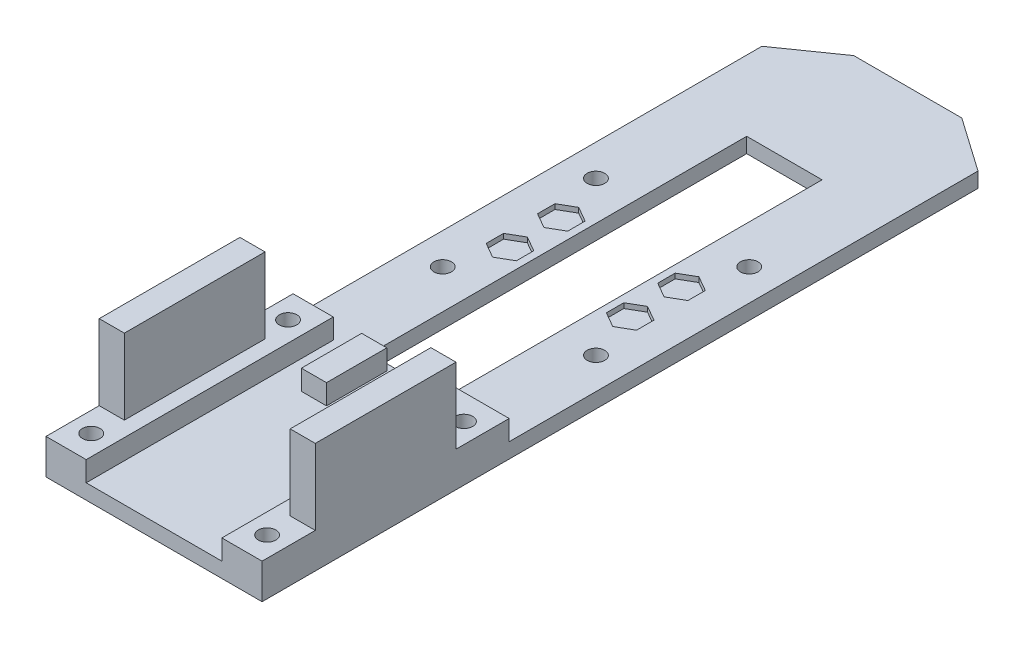
SolidWorks part; units mm, degrees
material "ABS"
ref_plane "Front Plane" through (0, 0, 0) normal (0, 0, 1) x (1, 0, 0)
ref_plane "Top Plane" through (0, 0, 0) normal (0, 1, 0) x (1, 0, 0)
ref_plane "Right Plane" through (0, 0, 0) normal (1, 0, 0) x (0, 0, -1)
sketch "Sketch1" plane through (0, 0, 0) normal (0, 1, 0) x (1, 0, 0)
  line L1 (21.5, -75) -> (-21.5, -75)
  line L2 (21.5, -75) -> (21.5, 75)
  line L3 (21.5, 75) -> (-21.5, 75)
  line L4 (-21.5, -75) -> (-21.5, 75)
  line L5 (21.5, -75) -> (-21.5, 75) construction
  line L6 (21.5, 75) -> (-21.5, -75) construction
  point P0 (0, 0)
  dimension "D1" = 150
  dimension "D2" = 43
extrude "Boss-Extrude1" add sketch "Sketch1" along normal blind 3
sketch "Sketch2" plane through (0, 3, 0) normal (0, 1, 0) x (1, 0, 0)
  line L0 (0, 75) -> (0, 38.94) construction
  line L1 (21.5, 75) -> (-21.5, 75) construction
  line L2 (0, 75) -> (15.25, 75) construction
  line L3 (15.25, 75) -> (15.25, 28.19) construction
  line L5 (15.25, 28.19) -> (-15.25, 28.19) construction
  line L6 (15.25, 28.19) -> (15.25, -2.31) construction
  line L7 (15.25, -2.31) -> (-15.25, -2.31) construction
  line L8 (-15.25, 28.19) -> (-15.25, -2.31) construction
  circle A0 centre (15.25, 28.19) radius 1.75
  circle A1 centre (-15.25, 28.19) radius 1.75
  circle A2 centre (-15.25, -2.31) radius 1.75
  circle A3 centre (15.25, -2.31) radius 1.75
  dimension "D6" = 3.5
  dimension "D7" = 3.5
  dimension "D8" = 3.5
  dimension "D9" = 3.5
  dimension "D1" = 36.06
  dimension "D2" = 15.25
  dimension "D3" = 46.81
  dimension "D4" = 30.5
  dimension "D5" = 30.5
extrude "Cut-Extrude1" cut sketch "Sketch2" against normal blind 10
sketch "Sketch3" plane through (0, 3, 0) normal (0, 1, 0) x (1, 0, 0)
  line L0 (-15.25, 28.19) -> (15.25, -2.31) construction
  line L1 (-15.25, 28.19) -> (15.25, 28.19) construction
  line L2 (-15.25, 28.19) -> (-15.25, -2.31) construction
  line L3 (-15.25, -2.31) -> (15.25, -2.31) construction
  line L4 (15.25, 28.19) -> (15.25, -2.31) construction
  line L6 (7.5, 50.44) -> (-7.5, 50.44)
  line L7 (7.5, 50.44) -> (7.5, -24.56)
  line L8 (7.5, -24.56) -> (-7.5, -24.56)
  line L9 (-7.5, 50.44) -> (-7.5, -24.56)
  line L10 (7.5, 50.44) -> (-7.5, -24.56) construction
  line L11 (7.5, -24.56) -> (-7.5, 50.44) construction
  point P6 (0, 12.94)
  dimension "D1" = 75
  dimension "D2" = 15
extrude "Cut-Extrude2" cut sketch "Sketch3" against normal blind 10
sketch "Sketch4" plane through (0, 3, 0) normal (0, 1, 0) x (1, 0, 0)
  line L0 (0, -24.56) -> (2.65, -24.56) construction
  line L1 (-7.5, -24.56) -> (7.5, -24.56) construction
  line L2 (2.65, -24.56) -> (2.65, -25.83) construction
  line L3 (8.15, -25.83) -> (-2.85, -25.83) construction
  line L4 (8.15, -37.83) -> (-2.85, -37.83) construction
  line L5 (-2.85, -25.83) -> (-7.85, -25.83)
  line L6 (-2.85, -25.83) -> (-2.85, -37.83)
  line L7 (-2.85, -37.83) -> (-7.85, -37.83)
  line L8 (-7.85, -25.83) -> (-7.85, -37.83)
  line L9 (8.15, -25.83) -> (13.15, -25.83)
  line L10 (8.15, -25.83) -> (8.15, -37.83)
  line L11 (8.15, -37.83) -> (13.15, -37.83)
  line L12 (13.15, -25.83) -> (13.15, -37.83)
  line L14 (2.65, -37.83) -> (6.7668, -37.83)
  line L15 (2.65, -37.83) -> (2.65, -36.33)
  line L16 (2.65, -36.33) -> (6.7668, -36.33)
  line L17 (6.7668, -37.83) -> (6.7668, -36.33)
  line L18 (2.65, -37.83) -> (6.7668, -37.83)
  line L19 (2.65, -37.83) -> (2.65, -41.33)
  line L20 (2.65, -41.33) -> (6.7668, -41.33)
  line L21 (6.7668, -37.83) -> (6.7668, -41.33)
  point P8 (2.65, -25.83)
  dimension "D1" = 2.65
  dimension "D2" = 1.27
  dimension "D3" = 11
  dimension "D4" = 5
  dimension "D5" = 5
  dimension "D6" = 12
  dimension "D7" = 12
  dimension "D8" = 1.5
  dimension "D9" = 3.5
extrude "Boss-Extrude2" add sketch "Sketch4" along normal blind 4 contours L6 L5 L8 L7 | L10 L9 L12 L11 | L19 L18 L21 L20 | L15 L14 L17 L16
sketch "Sketch5" plane through (0, 3, 0) normal (0, 1, 0) x (1, 0, 0)
  line L0 (-7.85, -25.83) -> (-21.5, -25.83) construction
  line L1 (-21.5, 75) -> (-21.5, -75) construction
  line L2 (13.15, -25.83) -> (21.5, -25.83) construction
  line L3 (21.5, -75) -> (21.5, 75) construction
  line L4 (-21.5, -75) -> (21.5, -75) construction
  line L5 (-21.5, -25.83) -> (-13.5, -25.83)
  line L6 (-21.5, -25.83) -> (-21.5, -75)
  line L7 (-21.5, -75) -> (-13.5, -75)
  line L8 (-13.5, -25.83) -> (-13.5, -75)
  line L10 (21.5, -25.83) -> (13.5, -25.83)
  line L11 (21.5, -25.83) -> (21.5, -75)
  line L12 (21.5, -75) -> (13.5, -75)
  line L13 (13.5, -25.83) -> (13.5, -75)
  dimension "D1" = 8
  dimension "D2" = 8
extrude "Boss-Extrude3" add sketch "Sketch5" along normal blind 4
sketch "Sketch7" plane through (0, 3, 0) normal (0, 1, 0) x (1, 0, 0)
  line L1 (13.15, -37.83) -> (13.5, -37.83)
  line L2 (13.15, -37.83) -> (13.15, -25.83)
  line L3 (13.15, -25.83) -> (13.5, -25.83)
  line L4 (13.5, -37.83) -> (13.5, -25.83)
extrude "Boss-Extrude4" add sketch "Sketch7" along normal blind 4
sketch "Sketch8" plane through (0, 7, 0) normal (0, 1, 0) x (1, 0, 0)
  line L0 (21.5, -75) -> (17.5, -75) construction
  line L1 (13.5, -75) -> (21.5, -75) construction
  line L2 (17.5, -75) -> (17.5, -70) construction
  line L3 (21.5, -25.83) -> (-21.5, -25.83) construction
  line L4 (0, -25.83) -> (0, -75) construction
  line L5 (-13.5, -75) -> (13.5, -75) construction
  line L6 (21.5, -50.415) -> (-21.5, -50.415) construction
  line L7 (21.5, -75) -> (21.5, -25.83) construction
  line L8 (-21.5, -25.83) -> (-21.5, -75) construction
  circle A0 centre (17.5, -70) radius 1.75
  circle A1 centre (17.5, -30.83) radius 1.75
  circle A2 centre (-17.5, -70) radius 1.75
  circle A3 centre (-17.5, -30.83) radius 1.75
  dimension "D2" = 3.5
  dimension "D1" = 5
extrude "Cut-Extrude3" cut sketch "Sketch8" against normal through all
sketch "Sketch9" plane through (0, 7, 0) normal (0, 1, 0) x (1, 0, 0)
  line L0 (21.5, -75) -> (21.5, -64.41) construction
  line L1 (21.5, -75) -> (21.5, -25.83) construction
  line L2 (0, -75) -> (0, -24.56) construction
  line L3 (21.5, -64.41) -> (16.5, -64.41)
  line L4 (21.5, -64.41) -> (21.5, -36.41)
  line L5 (21.5, -36.41) -> (16.5, -36.41)
  line L6 (16.5, -64.41) -> (16.5, -36.41)
  line L7 (-13.5, -75) -> (13.5, -75) construction
  line L8 (-7.5, -24.56) -> (7.5, -24.56) construction
  line L9 (-21.5, -36.41) -> (-16.5, -36.41)
  line L10 (-16.5, -64.41) -> (-16.5, -36.41)
  line L11 (-21.5, -64.41) -> (-16.5, -64.41)
  line L12 (-21.5, -64.41) -> (-21.5, -36.41)
  dimension "D1" = 10.59
  dimension "D2" = 5
  dimension "D3" = 28
extrude "Boss-Extrude5" add sketch "Sketch9" along normal blind 15
sketch "Sketch10" plane through (0, 0, 0) normal (0, -1, 0) x (1, 0, 0)
  circle A0 centre (-17.5, 70) radius 3
  circle A1 centre (-17.5, 30.83) radius 3
  circle A2 centre (17.5, 30.83) radius 3
  circle A3 centre (17.5, 70) radius 3
  dimension "D1" = 6
  dimension "D2" = 6
  dimension "D3" = 6
  dimension "D4" = 6
extrude "Cut-Extrude5" cut sketch "Sketch10" against normal blind 2
sketch "Sketch11" plane through (0, 3, 0) normal (0, 1, 0) x (1, 0, 0)
  line L0 (-21.5, 75) -> (-10.75, 75)
  line L1 (21.5, 75) -> (-21.5, 75) construction
  line L2 (-10.75, 75) -> (-21.5, 67.4728)
  line L3 (-21.5, 75) -> (-21.5, -25.83) construction
  line L4 (-21.5, 67.4728) -> (-21.5, 75)
  line L5 (0, 75) -> (0, 50.44) construction
  line L6 (7.5, 50.44) -> (-7.5, 50.44) construction
  line L7 (10.75, 75) -> (21.5, 67.4728)
  line L8 (21.5, 75) -> (10.75, 75)
  line L9 (21.5, 67.4728) -> (21.5, 75)
  dimension "D1" = 10.75
  dimension "D2" = 35
extrude "Cut-Extrude6" cut sketch "Sketch11" against normal through all
sketch "Sketch12" plane through (0, 3, 0) normal (0, 1, 0) x (1, 0, 0)
  line L0 (-21.5, 67.4728) -> (-21.5, 18.0128) construction
  line L1 (-21.5, 67.4728) -> (-21.5, -25.83) construction
  line L2 (-21.5, 18.0128) -> (-11.96, 18.0128) construction
  line L3 (-11.96, 18.0128) -> (-11.96, 7.7928) construction
  line L4 (0, 50.44) -> (0, -24.56) construction
  line L17 (-11.96, 21.4769) -> (-14.96, 19.7448)
  line L18 (-14.96, 19.7448) -> (-14.96, 16.2807)
  line L19 (-14.96, 16.2807) -> (-11.96, 14.5487)
  line L20 (-11.96, 14.5487) -> (-8.96, 16.2807)
  line L21 (-8.96, 16.2807) -> (-8.96, 19.7448)
  line L22 (-8.96, 19.7448) -> (-11.96, 21.4769)
  line L23 (-11.96, 11.2569) -> (-14.96, 9.5248)
  line L24 (-14.96, 9.5248) -> (-14.96, 6.0607)
  line L25 (-14.96, 6.0607) -> (-11.96, 4.3287)
  line L26 (-11.96, 4.3287) -> (-8.96, 6.0607)
  line L27 (-8.96, 6.0607) -> (-8.96, 9.5248)
  line L28 (-8.96, 9.5248) -> (-11.96, 11.2569)
  line L29 (7.5, 50.44) -> (-7.5, 50.44) construction
  line L30 (-7.5, -24.56) -> (7.5, -24.56) construction
  line L31 (8.96, 19.7448) -> (11.96, 21.4769)
  line L32 (8.96, 16.2807) -> (8.96, 19.7448)
  line L33 (11.96, 14.5487) -> (8.96, 16.2807)
  line L34 (14.96, 16.2807) -> (11.96, 14.5487)
  line L35 (14.96, 19.7448) -> (14.96, 16.2807)
  line L36 (11.96, 21.4769) -> (14.96, 19.7448)
  line L37 (8.96, 9.5248) -> (11.96, 11.2569)
  line L38 (8.96, 6.0607) -> (8.96, 9.5248)
  line L39 (11.96, 4.3287) -> (8.96, 6.0607)
  line L40 (14.96, 6.0607) -> (11.96, 4.3287)
  line L41 (14.96, 9.5248) -> (14.96, 6.0607)
  line L42 (11.96, 11.2569) -> (14.96, 9.5248)
  circle A0 centre (-11.96, 18.0128) radius 3 construction
  circle A1 centre (-11.96, 7.7928) radius 3 construction
  dimension "D1" = 49.46
  dimension "D2" = 9.54
  dimension "D3" = 10.22
  dimension "D4" = 6
  dimension "D5" = 6
extrude "Cut-Extrude7" cut sketch "Sketch12" against normal blind 1
